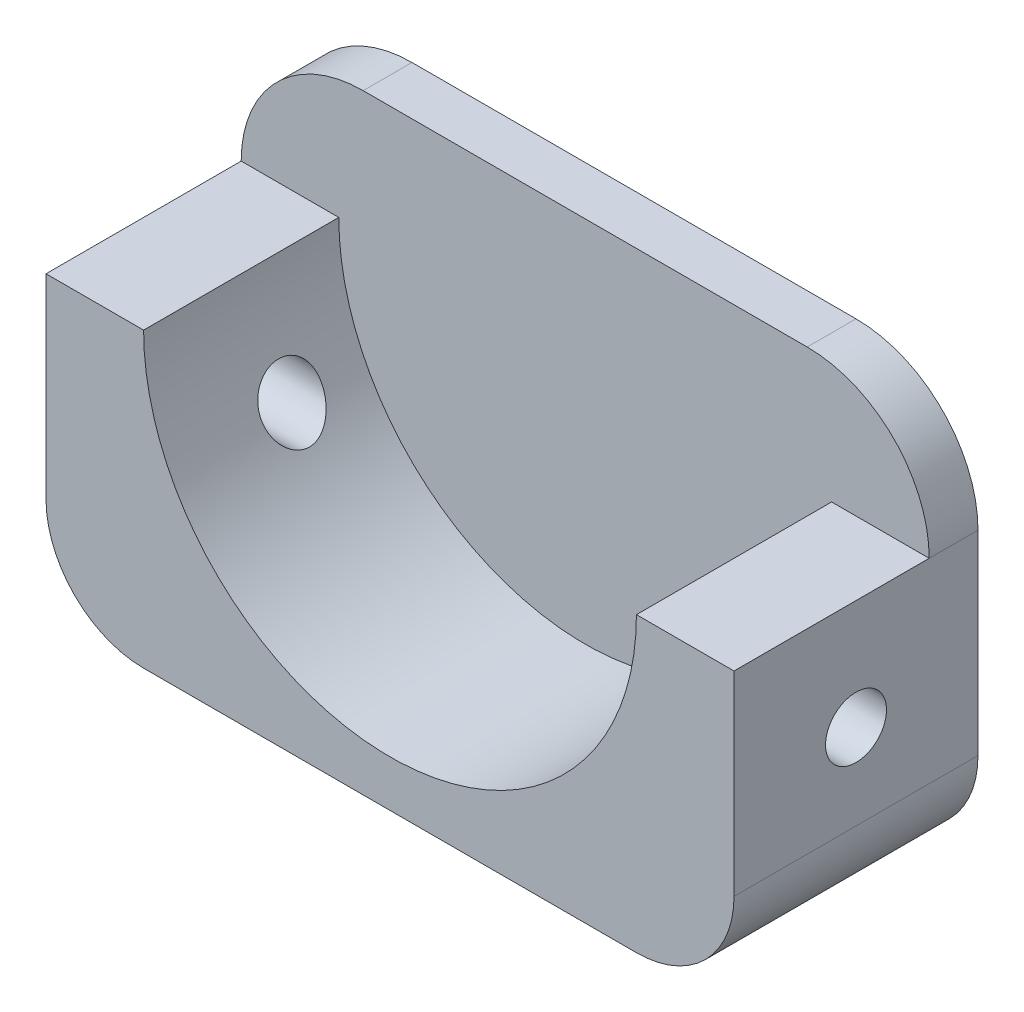
SolidWorks part; units mm, degrees
ref_plane "前视基准面" through (0, 0, 0) normal (0, 0, 1) x (1, 0, 0)
ref_plane "上视基准面" through (0, 0, 0) normal (0, 1, 0) x (1, 0, 0)
ref_plane "右视基准面" through (0, 0, 0) normal (1, 0, 0) x (0, 0, -1)
sketch "草图1" plane through (0, 0, 0) normal (0, 0, 1) x (1, 0, 0)
  line L0 (-10.1, 0) -> (-14.1, 0)
  line L1 (-14.1, 0) -> (-14.1, -12)
  line L2 (-14.1, -12) -> (14.1, -12)
  line L3 (0, -1000) -> (0, 49000) construction
  line L4 (14.1, 0) -> (14.1, -12)
  line L5 (10.1, 0) -> (14.1, 0)
  arc A0 (-10.1, 0) -> (10.1, 0) centre (0, 0) ccw
  point P7 (0, -12.2022)
  point P11 (0, -12)
  dimension "D1" = 20.2
  dimension "D2" = 4
  dimension "D3" = 12
extrude "凸台-拉伸1" add sketch "草图1" along normal blind 8
sketch "草图2" plane through (0, 0, 0) normal (0, 0, -1) x (-1, 0, 0)
  line L0 (-14.1, -12) -> (-14.1, 0) construction
  line L1 (14.1, -12) -> (-14.1, -12) construction
  line L2 (14.1, 0) -> (14.1, -12) construction
  line L3 (-14.1, -12) -> (-14.1, 0)
  line L4 (14.1, -12) -> (-14.1, -12)
  line L5 (14.1, 0) -> (14.1, -12)
  line L6 (-13.1837, 5) -> (13.1837, 5)
  arc A0 (14.1, 0) -> (13.1837, 5) centre (0, 0) ccw
  arc A1 (-13.1837, 5) -> (-14.1, 0) centre (0, 0) ccw
  dimension "D1" = 28.2
  dimension "D2" = 5
extrude "凸台-拉伸2" add sketch "草图2" along normal blind 2
sketch "草图3" plane through (-14.1, 0, 0) normal (-1, 0, 0) x (0, 0, 1)
  line L0 (3, -1012) -> (3, 48988) construction
  line L1 (8, -12) -> (-2, -12) construction
  line L2 (8, 0) -> (0, 0) construction
  circle A0 centre (3, -4.5) radius 1.25
  point P5 (3, -12)
  dimension "D1" = 2.5
  dimension "D2" = 4.5
extrude "切除-拉伸1" cut sketch "草图3" against normal through all
fillet "圆角1" radius 5 2 edges at (-13.1837, 5, -1) (13.1837, 5, -1)
fillet "圆角2" radius 4 2 edges at (14.1, -12, 3) (-14.1, -12, 3)
